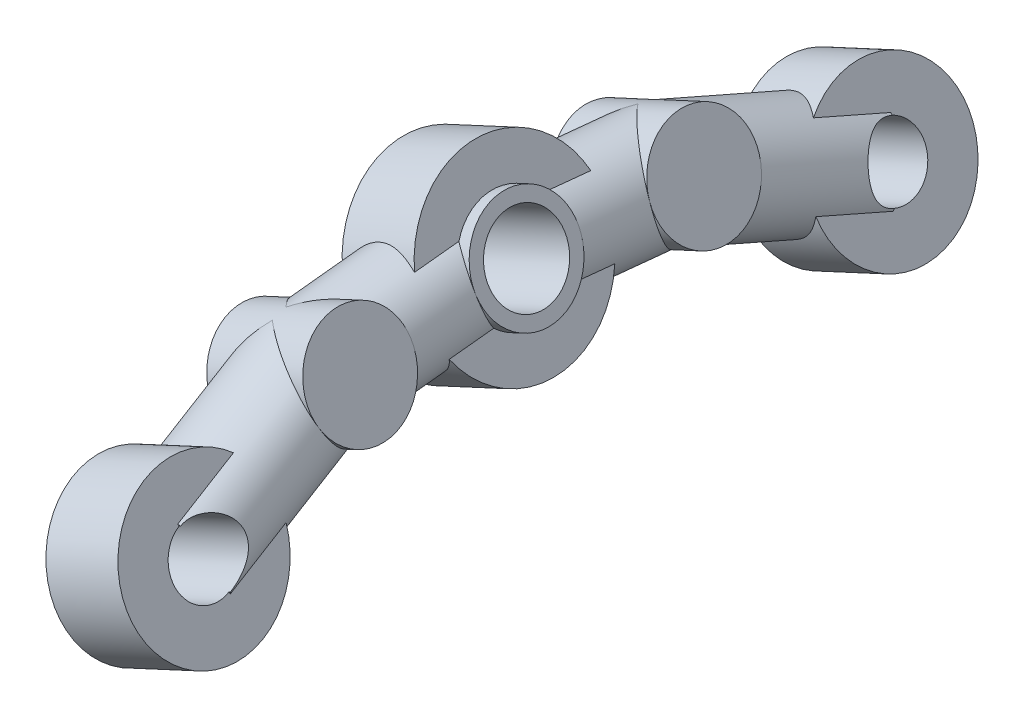
SolidWorks part; units mm, degrees
material "6061-T6 (SS)"
ref_plane "Alzado" through (0, 0, 0) normal (0, 0, 1) x (1, 0, 0)
ref_plane "Planta" through (0, 0, 0) normal (0, 1, 0) x (1, 0, 0)
ref_plane "Vista lateral" through (0, 0, 0) normal (1, 0, 0) x (0, 0, -1)
sketch3d "Sk_Arco_1"
  line L0 (430.9555, 383.6552, -26) -> (428.8507, 388.1906, -13)
  dimension "D1" = 13.9284
sweep "Arco_1" add path "Sk_Arco_1" circular profile diameter 8 parameters "D3"=8
sketch3d "Sk_Arco_2"
  line L0 (428.8507, 388.1906, -13) -> (428.4297, 389.0977, 0)
  dimension "D1" = 13.0384
sweep "Arco_2" add path "Sk_Arco_2" circular profile diameter 8 parameters "D3"=8
sketch3d "Sk_Arco_3"
  line L0 (428.4297, 389.0977, 0) -> (428.8507, 388.1906, 13)
  dimension "D1" = 13.0384
sweep "Arco_3" add path "Sk_Arco_3" circular profile diameter 8 parameters "D3"=8
sketch3d "Sk_Arco_4"
  line L0 (428.8507, 388.1906, 13) -> (430.9555, 383.6552, 26)
  dimension "D1" = 13.9284
sweep "Arco_4" add path "Sk_Arco_4" circular profile diameter 8 parameters "D3"=8
sketch3d "Sk_Arco_codo_1"
  line L0 (425.2224, 386.5067, -13) -> (432.479, 389.8744, -13)
  dimension "D1" = 8
sweep "Arco_codo_1" add path "Sk_Arco_codo_1" circular profile diameter 8 parameters "D3"=8
sketch3d "Sk_Arco_codo_2"
  line L0 (424.8014, 387.4138, 0) -> (432.058, 390.7815, 0)
  dimension "D1" = 8
sweep "Arco_codo_2" add path "Sk_Arco_codo_2" circular profile diameter 8 parameters "D3"=8
sketch3d "Sk_Arco_codo_3"
  line L0 (425.2224, 386.5067, 13) -> (432.479, 389.8744, 13)
  dimension "D1" = 8
sweep "Arco_codo_3" add path "Sk_Arco_codo_3" circular profile diameter 8 parameters "D3"=8
sketch3d "Sk_Boss_izq"
  line L0 (428.2343, 382.3923, -26) -> (433.6768, 384.9181, -26)
  dimension "D1" = 6
sweep "Boss_izq" add path "Sk_Boss_izq" circular profile diameter 12 parameters "D3"=12
sketch3d "Sk_Boss_dcho"
  line L0 (428.2343, 382.3923, 26) -> (433.6768, 384.9181, 26)
  dimension "D1" = 6
sweep "Boss_dcho" add path "Sk_Boss_dcho" circular profile diameter 12 parameters "D3"=12
sketch3d "Sk_Boss_centro"
  line L0 (425.7085, 387.8347, 0) -> (431.151, 390.3606, 0)
  dimension "D1" = 6
sweep "Boss_centro" add path "Sk_Boss_centro" circular profile diameter 14 parameters "D3"=14
sketch3d "Sk_Pivote_izq"
  line L0 (427.3272, 381.9713, -26) -> (434.5838, 385.3391, -26)
  dimension "D1" = 8
sweep "Pivote_izq" cut path "Sk_Pivote_izq" circular profile diameter 5 parameters "D3"=5
sketch3d "Sk_Pivote_dcho"
  line L0 (427.3272, 381.9713, 26) -> (434.5838, 385.3391, 26)
  dimension "D1" = 8
sweep "Pivote_dcho" cut path "Sk_Pivote_dcho" circular profile diameter 5 parameters "D3"=5
sketch3d "Sk_Taladro_tornillo"
  line L0 (424.8014, 387.4138, 0) -> (432.058, 390.7815, 0)
  dimension "D1" = 8
sweep "Taladro_tornillo" cut path "Sk_Taladro_tornillo" circular profile diameter 6 parameters "D3"=6
